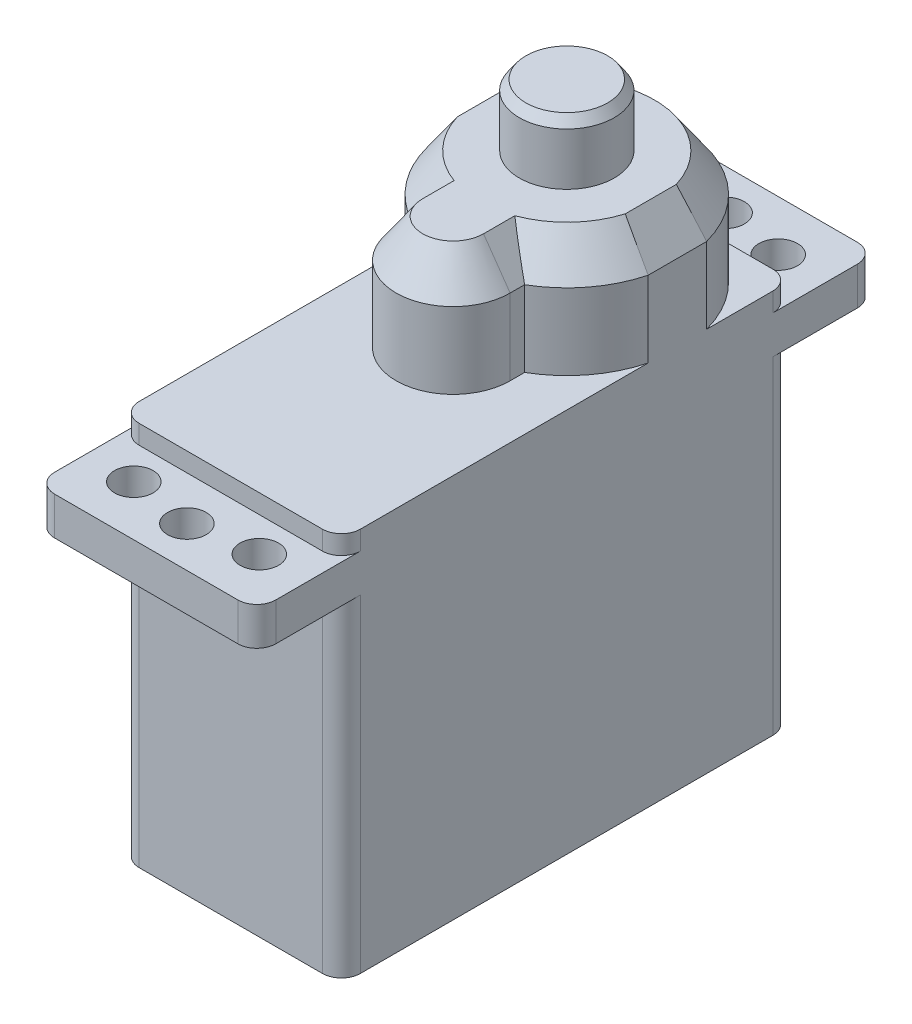
SolidWorks part; units mm, degrees
ref_plane "Front" through (0, 0, 0) normal (0, 0, 1) x (1, 0, 0)
ref_plane "Top" through (0, 0, 0) normal (0, 1, 0) x (1, 0, 0)
ref_plane "Right" through (0, 0, 0) normal (1, 0, 0) x (0, 0, -1)
sketch "Sketch1" plane through (0, 0, 0) normal (0, 1, 0) x (1, 0, 0)
  line L1 (-5.82, 11.85) -> (5.82, 11.85)
  line L2 (-5.82, 11.85) -> (-5.82, -11.85)
  line L3 (-5.82, -11.85) -> (5.82, -11.85)
  line L4 (5.82, 11.85) -> (5.82, -11.85)
  line L5 (-5.82, 11.85) -> (5.82, -11.85) construction
  line L6 (-5.82, -11.85) -> (5.82, 11.85) construction
  point P0 (0, 0)
  dimension "D1" = 23.7
  dimension "D2" = 11.64
extrude "Boss-Extrude1" add sketch "Sketch1" along normal blind 20.25
sketch "Sketch2" plane through (0, 0, 11.85) normal (0, 0, 1) x (1, 0, 0)
  line L0 (5.82, 20.25) -> (5.82, 0) construction
  line L1 (-5.82, 19.25) -> (5.82, 19.25)
  line L2 (-5.82, 19.25) -> (-5.82, 17.25)
  line L3 (-5.82, 17.25) -> (5.82, 17.25)
  line L4 (5.82, 19.25) -> (5.82, 17.25)
  line L5 (-5.82, 19.25) -> (5.82, 17.25) construction
  line L6 (-5.82, 17.25) -> (5.82, 19.25) construction
  line L7 (-5.82, 20.25) -> (5.82, 20.25) construction
  line L8 (0, 0) -> (0, 20.25) construction
  point P0 (0, 18.25)
  dimension "D1" = 1
  dimension "D2" = 2
  dimension "D3" = 11.64
extrude "Boss-Extrude2" add sketch "Sketch2" along normal blind 4.45
sketch "Sketch3" plane through (0, 0, -11.85) normal (0, 0, -1) x (-1, 0, 0)
  line L0 (0, 0) -> (0, 20.25) construction
  line L1 (-5.82, 20.25) -> (5.82, 20.25) construction
  line L2 (5.82, 20.25) -> (5.82, 0) construction
  line L3 (-5.82, 19.25) -> (5.82, 19.25)
  line L4 (-5.82, 19.25) -> (-5.82, 17.25)
  line L5 (-5.82, 17.25) -> (5.82, 17.25)
  line L6 (5.82, 19.25) -> (5.82, 17.25)
  line L7 (-5.82, 19.25) -> (5.82, 17.25) construction
  line L8 (-5.82, 17.25) -> (5.82, 19.25) construction
  point P5 (0, 18.25)
  dimension "D1" = 1
  dimension "D2" = 2
extrude "Boss-Extrude3" add sketch "Sketch3" along normal blind 4.45
fillet "Fillet1" radius 1 12 edges at (-5.82, 19.75, 11.85) (-5.82, 19.75, -11.85) (5.82, 19.75, -11.85) (5.82, 19.75, 11.85) (5.82, 18.25, 16.3) (-5.82, 18.25, 16.3) (-5.82, 18.25, -16.3) (5.82, 18.25, -16.3) (-5.82, 8.625, -11.85) (5.82, 8.625, -11.85) (5.82, 8.625, 11.85) (-5.82, 8.625, 11.85)
sketch "Sketch4" plane through (0, 20.25, 0) normal (0, 1, 0) x (1, 0, 0)
  line L0 (0, 11.85) -> (0, -11.85) construction
  line L1 (4.82, 11.85) -> (-4.82, 11.85) construction
  line L2 (4.82, -11.85) -> (-4.82, -11.85) construction
  line L3 (-3, -0.15) -> (-3, 0.6112)
  line L4 (3, -0.15) -> (3, 0.6112)
  line L9 (-5.82, 4.2922) -> (-5.82, 7.3682)
  line L10 (-5.82, 10.85) -> (-5.82, -10.85) construction
  line L11 (5.82, 4.2922) -> (5.82, 7.3682)
  line L12 (5.82, -10.85) -> (5.82, 10.85) construction
  line L13 (-4.82, 11.85) -> (4.82, 11.85) construction
  arc A1 (-3, -0.15) -> (3, -0.15) centre (0, -0.15) ccw
  arc A5 (5.82, 7.3682) -> (-5.82, 7.3682) centre (0, 5.8302) ccw
  arc A6 (-5.82, 4.2922) -> (-3, 0.6112) centre (0, 5.8302) ccw
  arc A7 (3, 0.6112) -> (5.82, 4.2922) centre (0, 5.8302) ccw
  point P22 (0, -3.15)
  dimension "D2" = 12.0396
  dimension "D1" = 6
  dimension "D3" = 15
extrude "Boss-Extrude4" add sketch "Sketch4" along normal blind 6
chamfer "Chamfer2" distance 2 angle 35 8 edges at (3, 26.25, -0.2306) (0, 26.25, 3.15) (-3, 26.25, -0.2306) (-4.7786, 26.25, -2.1693) (-5.82, 26.25, -5.8302) (0, 26.25, -11.85) (5.82, 26.25, -5.8302) (4.7786, 26.25, -2.1693) first distance on face at (3, 23.25, -0.2306) first distance on face at (0, 23.25, 1.65) first distance on face at (-3, 23.25, -0.2306) first distance on face at (-4.5943, 23.25, -2.3105) first distance on face at (-5.82, 17.4688, -1.4576) first distance on face at (0, 22.65, -9.5572) first distance on face at (5.82, 17.4688, -1.4576) first distance on face at (4.5943, 23.25, -2.3105)
sketch "Sketch5" plane through (0, 26.25, 0) normal (0, 1, 0) x (1, 0, 0)
  circle A1 centre (0, 5.8302) radius 2.5
  dimension "D1" = 5
extrude "Boss-Extrude5" add sketch "Sketch5" along normal blind 3.25
sketch "Sketch6" plane through (0, 0, -11.85) normal (0, 0, -1) x (-1, 0, 0)
  line L0 (-1.6, 3.6) -> (-1.6, 2.4)
  line L1 (-3, 5) -> (3, 5)
  line L2 (-3, 5) -> (-3, 1)
  line L3 (-3, 1) -> (3, 1)
  line L4 (3, 5) -> (3, 1)
  line L5 (-3, 5) -> (3, 1) construction
  line L6 (-3, 1) -> (3, 5) construction
  line L7 (-1.6, 2.4) -> (1.6, 2.4)
  line L8 (1.6, 3.6) -> (1.6, 2.4)
  line L9 (-1.6, 3.6) -> (1.6, 3.6)
  line L11 (-4.82, 0) -> (4.82, 0) construction
  line L12 (0, 0) -> (0, 17.25) construction
  line L14 (-4.82, 17.25) -> (4.82, 17.25) construction
  point P0 (0, 3)
  dimension "D1" = 6
  dimension "D2" = 4
  dimension "D4" = 5
  dimension "D3" = 1.4
extrude "Boss-Extrude6" add sketch "Sketch6" along normal blind 1.5
fillet "Fillet2" radius 0.5 8 edges at (-1.6, 2.4, -12.6) (1.6, 2.4, -12.6) (1.6, 3.6, -12.6) (-1.6, 3.6, -12.6) (3, 1, -12.6) (-3, 1, -12.6) (-3, 5, -12.6) (3, 5, -12.6)
chamfer "Chamfer3" distance 0.5 angle 35 1 edges at (0, 29.5, -3.3302) first distance on face at (0, 29.5, -3.3302)
sketch "Sketch7" plane through (0, 19.25, 0) normal (0, 1, 0) x (1, 0, 0)
  line L0 (0, 16.3) -> (0, -16.3) construction
  line L1 (-4.82, 16.3) -> (4.82, 16.3) construction
  line L2 (4.82, -16.3) -> (-4.82, -16.3) construction
  line L3 (-5.82, 13.6525) -> (5.82, 13.6525) construction
  line L6 (-5.82, 15.3) -> (-5.82, 10.85) construction
  line L9 (5.82, 15.3) -> (5.82, 10.85) construction
  line L10 (-5.82, -13.6525) -> (5.82, -13.6525) construction
  line L11 (-5.82, -15.3) -> (-5.82, -10.85) construction
  line L12 (5.82, -15.3) -> (5.82, -10.85) construction
  circle A0 centre (0, -14.1605) radius 1.016
  circle A1 centre (0, 14.1605) radius 1.016
  circle A6 centre (-3.302, 13.6525) radius 1.016
  circle A7 centre (3.302, 13.6525) radius 1.016
  circle A8 centre (-3.302, -13.6525) radius 1.016
  circle A9 centre (3.302, -13.6525) radius 1.016
  dimension "D1" = 2.032
  dimension "D2" = 2.032
  dimension "D5" = 2.032
  dimension "D6" = 2.032
  dimension "D7" = 2.032
  dimension "D8" = 2.032
  dimension "D3" = 28.321
  dimension "D4" = 14.1605
  dimension "D9" = 27.305
  dimension "D10" = 3.302
  dimension "D11" = 3.302
  dimension "D12" = 3.302
  dimension "D13" = 3.302
  dimension "D14" = 13.6525
extrude "Cut-Extrude1" cut sketch "Sketch7" against normal up to next
fillet "Fillet3" radius 0.5 8 edges at (-2.8536, 1.1464, -13.35) (-2.8536, 4.8536, -13.35) (2.8536, 4.8536, -13.35) (2.8536, 1.1464, -13.35) (0, 1, -13.35) (3, 3, -13.35) (-3, 3, -13.35) (0, 5, -13.35)
